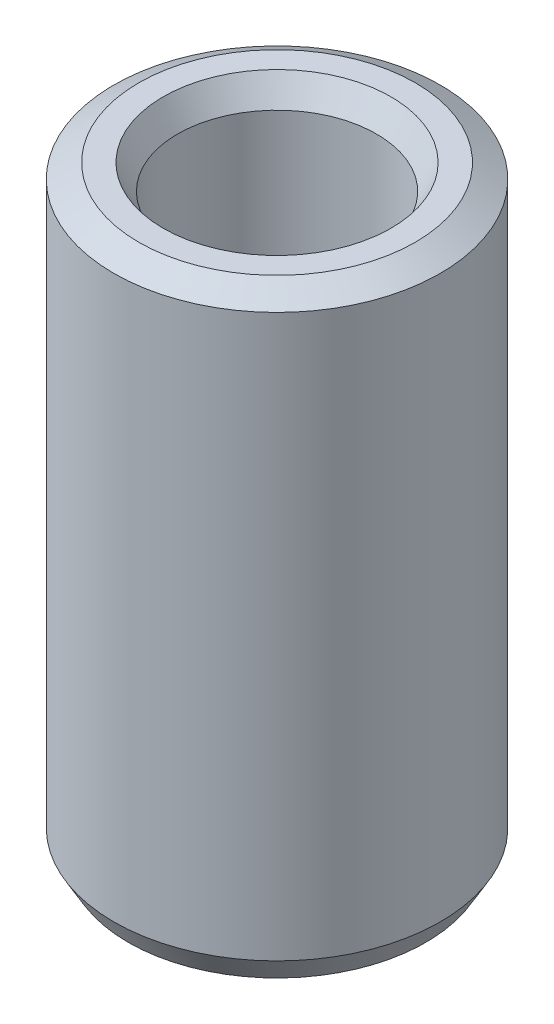
SolidWorks part; units mm, degrees
ref_plane "Front Plane" through (0, 0, 0) normal (0, 0, 1) x (1, 0, 0)
ref_plane "Top Plane" through (0, 0, 0) normal (0, 1, 0) x (1, 0, 0)
ref_plane "Right Plane" through (0, 0, 0) normal (1, 0, 0) x (0, 0, -1)
sketch "Sketch1" plane through (0, 0, 0) normal (0, 1, 0) x (1, 0, 0)
  circle A0 centre (0, 0) radius 10
  dimension "SLEEVE_OD" = 20
extrude "Boss-Extrude1" add sketch "Sketch1" along normal blind 36.8283
sketch "Sketch2" plane through (0, 0, 0) normal (0, 1, 0) x (1, 0, 0)
  circle A0 centre (0, 0) radius 6.0953
  dimension "BORE_D" = 12.1905
extrude "Cut-Extrude1" cut sketch "Sketch2" along normal through all
chamfer "Chamfer1" distance 0.8845 angle 60 4 edges at (0, 36.8283, 6.0953) (0, 0, 6.0953) (0, 0, 10) (0, 36.8283, 10) first distance on face at (0, 36.8283, 6.0953) first distance on face at (0, 0, 6.0953) first distance on face at (0, 36.8283, 10)
